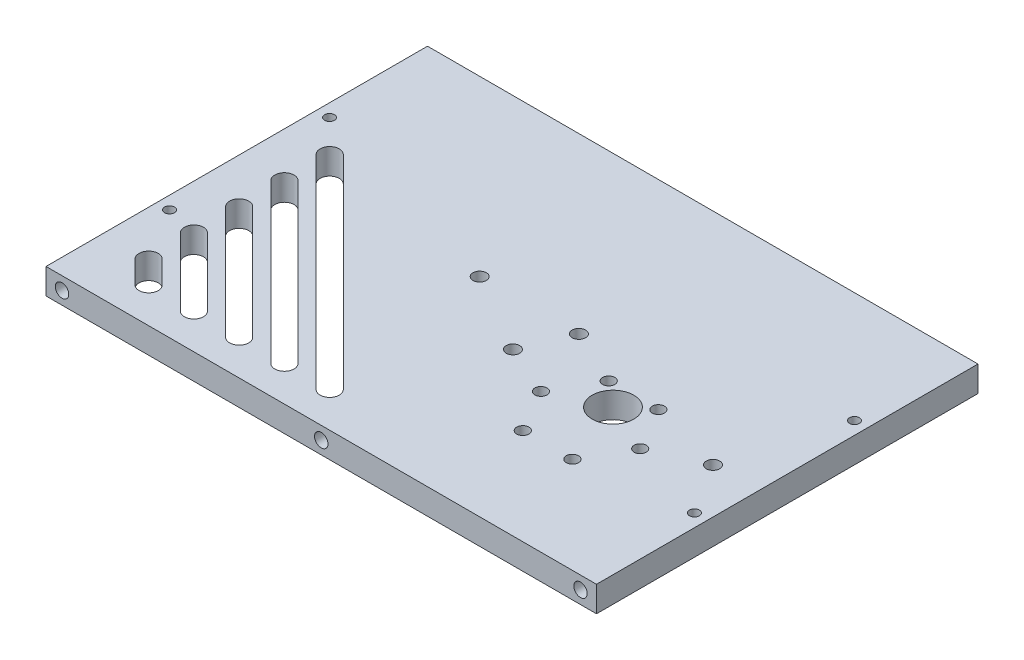
SolidWorks part; units mm, degrees
ref_plane "Front Plane" through (0, 0, 0) normal (1, 0, 0) x (0, 1, 0)
ref_plane "Top Plane" through (0, 0, 0) normal (0, 0, 1) x (0, 1, 0)
ref_plane "Right Plane" through (0, 0, 0) normal (0, 1, 0) x (-1, 0, 0)
sketch "Sketch1" plane through (0, 0, 0) normal (0, 1, 0) x (-1, 0, 0)
  line L3 (172, 0) -> (0, 0)
  line L10 (0, 119.2019) -> (172, 119.2019)
  line L15 (172, 119.2019) -> (172, 0)
  line L17 (0, 119.2019) -> (0, 0)
  point P16 (-5.5507, 58)
  point P19 (0, 0)
  point P27 (172, 0)
  dimension "D1" = 172
  dimension "D3" = 119.2019
extrude "Boss-Extrude1" add sketch "Sketch1" along normal blind 8 contours L10 L17 L3 L15 region at (-86, 0, 59.6009)
sketch "Sketch2" plane through (0, 0, 0) normal (0, -1, 0) x (1, 0, 0)
  line L0 (-95.9294, 8) -> (44.9505, 8) construction
  line L1 (-153.4835, 111.2019) -> (20.1803, 111.2019) construction
  line L2 (-30.5825, 54.2019) -> (46.7007, 54.2019) construction
  line L3 (-63.85, 68.025) -> (-63.85, 78.1366) construction
  line L4 (-172, 119.2019) -> (-172, 0) construction
  line L5 (-101.2651, 57.2019) -> (-70.3113, 57.2019) construction
  line L6 (-86, 47.6039) -> (-86, 23.5623) construction
  line L7 (-26.85, 55.8014) -> (-26.85, 50055.8014) construction
  line L8 (-12, 25.1758) -> (-12, 59.1601) construction
  line L9 (-158, 86.9887) -> (-136.7868, 108.2019) construction
  line L10 (-160.1213, 89.11) -> (-138.9081, 110.3232)
  line L11 (-155.8787, 84.8674) -> (-134.6655, 106.0806)
  line L12 (-158, 72.8466) -> (-122.6447, 108.2019) construction
  line L13 (-160.1213, 74.9679) -> (-124.766, 110.3232)
  line L14 (-155.8787, 70.7252) -> (-120.5233, 106.0806)
  line L15 (-158, 58.7044) -> (-108.5025, 108.2019) construction
  line L16 (-160.1213, 60.8257) -> (-110.6238, 110.3232)
  line L17 (-155.8787, 56.5831) -> (-106.3812, 106.0806)
  line L18 (-158, 44.5623) -> (-94.3604, 108.2019) construction
  line L19 (-160.1213, 46.6836) -> (-96.4817, 110.3232)
  line L20 (-155.8787, 42.441) -> (-92.2391, 106.0806)
  line L21 (-161, 125.2536) -> (-161, 20.8087) construction
  line L22 (0, 119.2019) -> (0, 0) construction
  line L23 (-45.35, 9.2203) -> (-45.35, -95.2246) construction
  line L24 (-158, 101.1308) -> (-150.9289, 108.2019) construction
  line L25 (-145.2721, 95.474) -> (-142.4437, 92.6456) construction
  line L26 (-138.201, 88.4029) -> (-135.3726, 85.5745) construction
  line L27 (-131.1299, 81.3318) -> (-128.3015, 78.5034) construction
  line L28 (-160.1213, 103.2522) -> (-153.0503, 110.3232)
  line L29 (-155.8787, 99.0095) -> (-148.8076, 106.0806)
  line L30 (-149.5147, 99.7166) -> (-152.3431, 102.545) construction
  line L31 (-172, 119.2019) -> (-172, 0) construction
  line L32 (-172, 0) -> (0, 0) construction
  line L33 (-45.35, 75.7019) -> (-45.35, 9.0934) construction
  line L35 (0, 119.2019) -> (-172, 119.2019) construction
  line L36 (0, 119.2019) -> (0, 0) construction
  circle A7 centre (-45.35, 68.7019) radius 6.5
  circle A9 centre (-45.35, 75.7019) radius 18.5 construction
  arc A11 (-160.1213, 89.11) -> (-155.8787, 84.8674) centre (-158, 86.9887) ccw
  arc A12 (-134.6655, 106.0806) -> (-138.9081, 110.3232) centre (-136.7868, 108.2019) ccw
  arc A13 (-160.1213, 74.9679) -> (-155.8787, 70.7252) centre (-158, 72.8466) ccw
  arc A14 (-120.5233, 106.0806) -> (-124.766, 110.3232) centre (-122.6447, 108.2019) ccw
  arc A15 (-160.1213, 60.8257) -> (-155.8787, 56.5831) centre (-158, 58.7044) ccw
  arc A16 (-106.3812, 106.0806) -> (-110.6238, 110.3232) centre (-108.5025, 108.2019) ccw
  arc A17 (-160.1213, 46.6836) -> (-155.8787, 42.441) centre (-158, 44.5623) ccw
  arc A18 (-92.2391, 106.0806) -> (-96.4817, 110.3232) centre (-94.3604, 108.2019) ccw
  arc A19 (-160.1213, 103.2522) -> (-155.8787, 99.0095) centre (-158, 101.1308) ccw
  arc A20 (-148.8076, 106.0806) -> (-153.0503, 110.3232) centre (-150.9289, 108.2019) ccw
  circle A21 centre (-45.35, 75.7019) radius 15.5 construction
  circle A22 centre (-60.85, 75.7019) radius 1.9
  circle A23 centre (-53.1, 89.1253) radius 1.9
  circle A24 centre (-37.6, 89.1253) radius 1.9
  circle A25 centre (-29.85, 75.7019) radius 1.9
  circle A26 centre (-37.6, 62.2785) radius 1.9
  circle A27 centre (-53.1, 62.2785) radius 1.9
  circle A32 centre (-45.35, 68.7019) radius 31.25 construction
  circle A33 centre (-76.6, 68.7019) radius 2.1
  circle A34 centre (-45.35, 99.9519) radius 2.1 construction
  circle A35 centre (-14.1, 68.7019) radius 2.1
  circle A36 centre (-45.35, 37.4519) radius 2.1 construction
  circle A37 centre (-70.5, 54.2019) radius 2.1
  circle A38 centre (-101.5, 54.2019) radius 2.1
  point P24 (-154.4645, 104.6664)
  point P45 (-147.3934, 97.5953)
  point P50 (-140.3223, 90.5242)
  point P57 (-133.2513, 83.4532)
  point P64 (-126.1802, 76.3821)
  dimension "D14" = 31
  dimension "D15" = 3.8
  dimension "D2" = 37
  dimension "D6" = 13
  dimension "D3" = 62.5
  dimension "D9" = 4.2
  dimension "D7" = 45
  dimension "D8" = 6
  dimension "D11" = 4
  dimension "D13" = 7
  dimension "D5" = 8
  dimension "D10" = 8
  dimension "D4" = 46.2019
  dimension "D17" = 12
  dimension "D19" = 10
  dimension "D20" = 11
  dimension "D12" = 31
  dimension "D21" = 3
  dimension "D16" = 6
  dimension "D18" = 4
extrude "Cut-Extrude1" cut sketch "Sketch2" against normal up to next
sketch "Sketch3" plane through (0, 0, 0) normal (0, 0, -1) x (1, 0, 0)
  line L2 (0, -4) -> (50000, -4) construction
  line L3 (0, -8) -> (0, 0) construction
  line L4 (-172, -8) -> (-172, 0) construction
  line L5 (-86, 0) -> (-86, -8) construction
  line L6 (-172, 0) -> (0, 0) construction
  line L7 (-172, -8) -> (0, -8) construction
  circle A0 centre (-5, -4) radius 2.1
  circle A1 centre (-167, -4) radius 2.1
  circle A2 centre (-86, -4) radius 2.1
  point P11 (0, -4)
  dimension "D1" = 4.2
  dimension "D3" = 5
  dimension "D2" = 5
extrude "Cut-Extrude2" cut sketch "Sketch3" against normal blind 15
extrude "Cut-Extrude3" cut sketch "Sketch3<3>" along normal blind 15 from surface starting at face at (-86, 4, 119.2019)
sketch "Sketch3<3>" plane through (0, 0, 0) normal (0, 0, -1) x (1, 0, 0) same geometry as "Sketch3"
sketch "Sketch4" plane through (0, 0, 0) normal (0, -1, 0) x (1, 0, 0)
  line L0 (-172, 59.6009) -> (0, 59.6009) construction
  line L1 (-168, 84.6009) -> (-4, 84.6009) construction
  line L2 (-168, 84.6009) -> (-168, 34.6009) construction
  line L3 (-168, 34.6009) -> (-4, 34.6009) construction
  line L4 (-4, 84.6009) -> (-4, 34.6009) construction
  line L5 (-172, 119.2019) -> (-172, 0) construction
  line L6 (0, 119.2019) -> (0, 0) construction
  circle A0 centre (-168, 84.6009) radius 1.55
  circle A1 centre (-168, 34.6009) radius 1.55
  circle A2 centre (-4, 34.6009) radius 1.55
  circle A3 centre (-4, 84.6009) radius 1.55
  point P14 (0, 0)
  dimension "D1" = 3.1
  dimension "D3" = 4
  dimension "D4" = 50
extrude "Cut-Extrude4" cut sketch "Sketch4" against normal up to next
equation "\"MotorDriverLength\"= 60mm"
equation "\"MotorLength\"= 60"
equation "\"MotorDriverWidth\"=44"
equation "\"MotorWidth\"= 37"
equation "\"InnerWallThickness\"=3"
equation "\"BatteryWidth\"= 60"
equation "\"OuterWallThickness\" = 8"
equation "\"CompartmentHeight\"=37"
equation "\"CompartmentWidth\"= \"MotorDriverLength\""
equation "\"MotorDiameter\"=37"
equation "\"BatteryHeight\"=24.2019"
equation "\"MotorDriverHeight\"=28"
equation "\"CircuitHeight\"=30"
equation "\"FanThickness\"= 10"
equation "\"FanHeight\"=50"
equation "\"D1@Boss-Extrude1\" = \"OuterWallThickness\""
equation "\"MotorShaftHole\"=12"
equation "\"BearingBore\"=4"
equation "\"MinShinWidth\"= 20"
equation "\"ShinThickness\"=10"
equation "\"PivotDistance\"=30"
equation "\"ThighLength\"= 200"
equation "\"HipBore\"=27"
equation "\"ThighThickness\"=20"
equation "\"MaxBending\"=135"
equation "\"MaxStretchingAngle\"= 140"
equation "\"ThighJointDistance\"=157.485"
equation "\"ShinLength\"=120"
equation "\"BearingDiameter\"= 10"
equation "\"D2@Sketch2\"=\"MotorDiameter\""
equation "\"D6@Sketch2\"=\"MotorShaftHole\"+1"
equation "\"D5@Sketch2\"=\"OuterWallThickness\""
equation "\"D10@Sketch2\"=\"OuterWallThickness\""
equation "\"D4@Sketch2\"=\"BatteryHeight\"+\"OuterWallThickness\"*1.5+10"
equation "\"GearboxDiameter\"= 62.5"
equation "\"D1@Sketch1\" = \"ChessisInnerWidth\""
equation "\"ChessisInnerWidth\"= \"OuterWallThickness\" * 2 + \"MotorDriverLength\" + \"MotorDiameter\" + \"InnerWallThickness\" * 3 + \"CircuitLength\""
equation "\"CircuitLength\"=50"
equation "\"D3@Sketch1\" = \"ChessisHeight\""
equation "\"D3@Sketch2\"=\"GearboxDiameter\""
equation "\"D17@Sketch2\"=\"OuterWallThickness\"+4"
equation "\"D20@Sketch2\"=\"OuterWallThickness\"+3"
equation "\"ChessisHeight\"= \"BatteryHeight\" + 10 + \"InnerWallThickness\" + \"MotorDriverHeight\"*2 + 10 + \"OuterWallThickness\" * 2"
equation "\"D3@Sketch4\"=\"OuterWallThickness\"/2"
equation "\"D2@Sketch4\"=\"OuterWallThickness\"/2"
